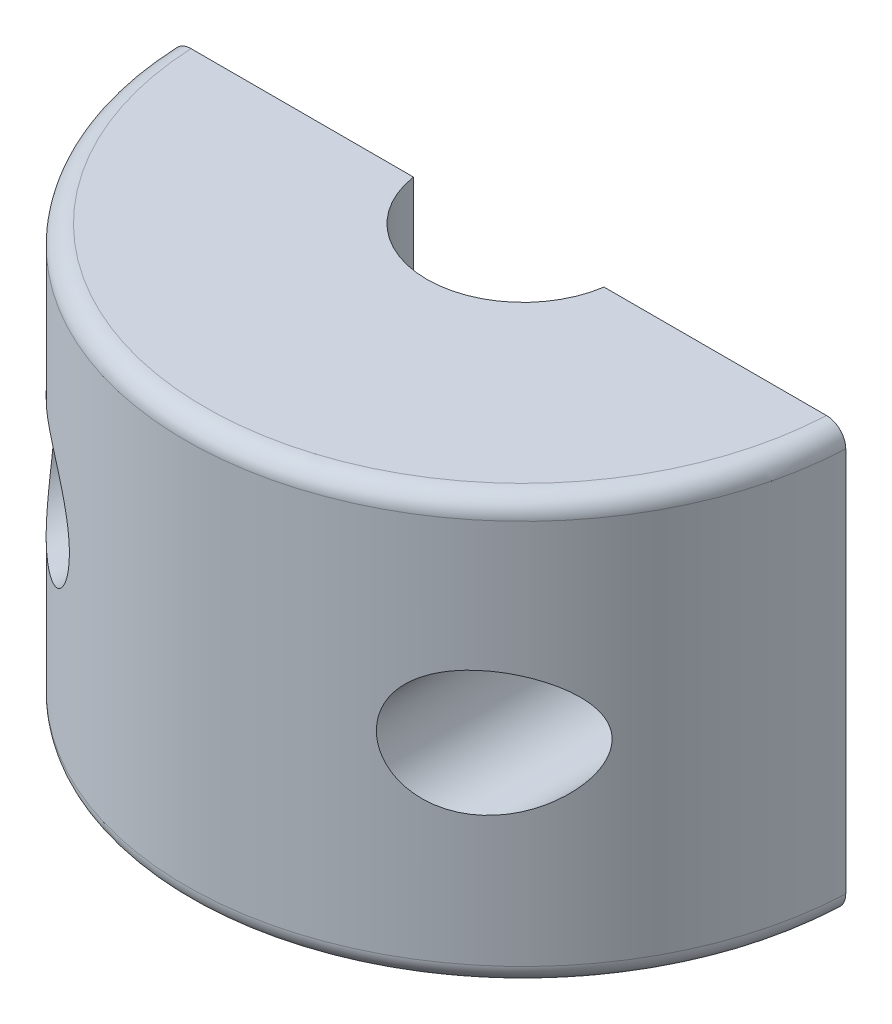
SolidWorks part; units mm, degrees
ref_plane "Front Plane" through (0, 0, 0) normal (0, 0, 1) x (1, 0, 0)
ref_plane "Top Plane" through (0, 0, 0) normal (0, 1, 0) x (1, 0, 0)
ref_plane "Right Plane" through (0, 0, 0) normal (1, 0, 0) x (0, 0, -1)
sketch "Sketch2" plane through (0, 0, 0) normal (0, 1, 0) x (1, 0, 0)
  line L0 (4.9434, -0.75) -> (17.4839, -0.75)
  line L1 (-4.9434, -0.75) -> (-17.4839, -0.75)
  arc A0 (-4.9434, -0.75) -> (4.9434, -0.75) centre (0, 0) ccw
  arc A1 (-17.4839, -0.75) -> (17.4839, -0.75) centre (0, 0) ccw
  dimension "D1" = 0
  dimension "D2" = 5
  dimension "D3" = 17.5
  dimension "D4" = 0.75
extrude "Boss-Extrude1" add sketch "Sketch2" along normal blind 22
sketch "Sketch3" plane through (0, 0, 0.75) normal (0, 0, -1) x (-1, 0, 0)
  line L0 (11.2137, 22) -> (11.2137, 0) construction
  line L1 (4.9434, 22) -> (17.4839, 22) construction
  line L2 (4.9434, 0) -> (17.4839, 0) construction
  line L3 (-11.2137, 0) -> (-11.2137, 22) construction
  line L4 (-17.4839, 0) -> (-4.9434, 0) construction
  line L5 (-17.4839, 22) -> (-4.9434, 22) construction
  circle A0 centre (11.2137, 11) radius 1.75
  circle A1 centre (-11.2137, 11) radius 1.75
  dimension "D1" = 3.5
extrude "Cut-Extrude1" cut sketch "Sketch3" against normal blind 22
ref_plane "Plane1" through (0, 0, 5.25) normal (0, 0, -1) x (-1, 0, 0)
sketch "Sketch4" plane through (0, 0, 5.25) normal (0, 0, -1) x (-1, 0, 0)
  circle A0 centre (-11.2137, 11) radius 3.25
  circle A1 centre (11.2137, 11) radius 3.25
  dimension "D1" = 6.5
extrude "Cut-Extrude2" cut sketch "Sketch4" against normal blind 22
fillet "Fillet1" radius 1 2 edges at (0, 0, 17.5) (0, 22, 17.5)
